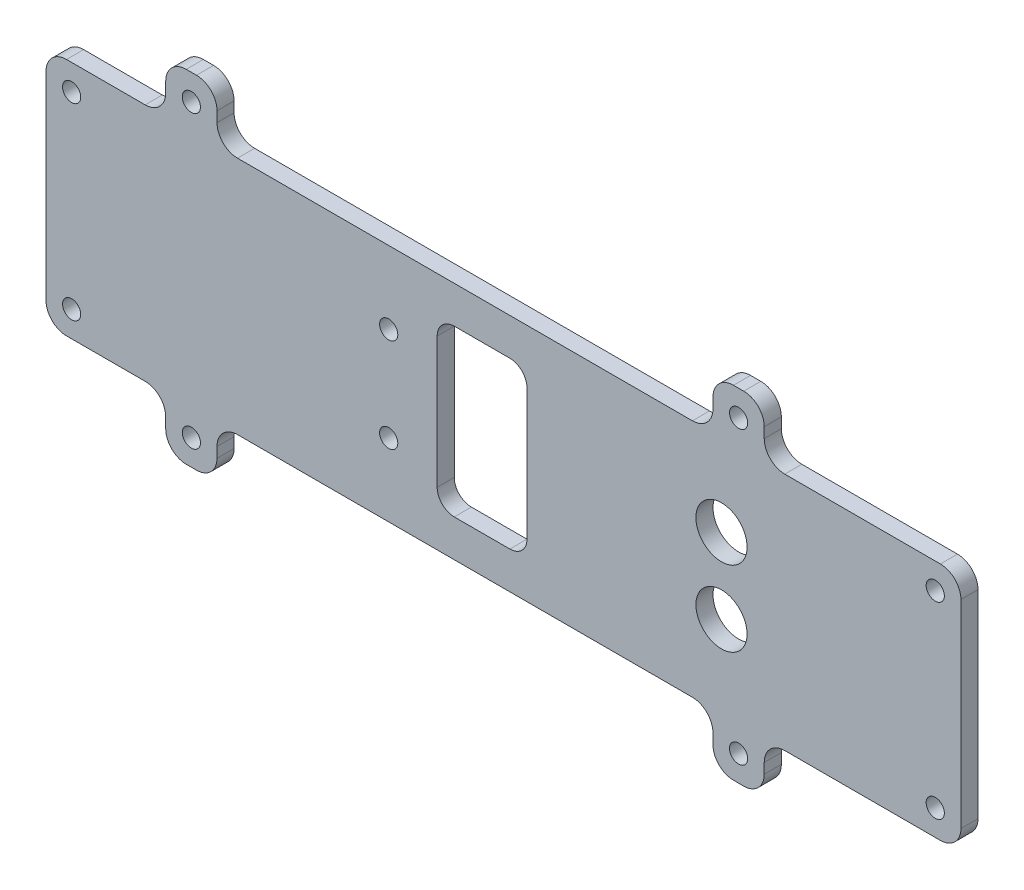
SolidWorks part; units mm, degrees
material "PC High Viscosity"
ref_plane "Front Plane" through (0, 0, 0) normal (0, 0, 1) x (1, 0, 0)
ref_plane "Top Plane" through (0, 0, 0) normal (0, 1, 0) x (1, 0, 0)
ref_plane "Right Plane" through (0, 0, 0) normal (1, 0, 0) x (0, 0, -1)
ref_plane "Plane1" through (0, 0, 0) normal (0, 0, -1) x (-1, 0, 0)
sketch "Sketch1" plane through (0, 0, 0) normal (0, 0, -1) x (-1, 0, 0)
  line L0 (-127, -44.45) -> (127, -44.45)
  line L1 (127, -44.45) -> (127, 44.45)
  line L2 (127, 44.45) -> (-127, 44.45)
  line L3 (-127, 44.45) -> (-127, -44.45)
  line L4 (13.5, 27.5) -> (13.5, -27.5)
  line L5 (13.5, -27.5) -> (-13.5, -27.5)
  line L6 (-13.5, -27.5) -> (-13.5, 27.5)
  line L7 (-13.5, 27.5) -> (13.5, 27.5)
  line L8 (0, 41.275) -> (0, -41.275) construction
  line L9 (-127, 0) -> (127, 0) construction
  line L10 (0, 27.5) -> (0, -27.5) construction
  circle A0 centre (28.58, 27.5) radius 1.85 construction
  circle A1 centre (18.58, 27.5) radius 1.85 construction
  circle A2 centre (18.58, -27.5) radius 1.85 construction
  circle A3 centre (28.58, -27.5) radius 1.85 construction
  circle A4 centre (-88.9, 14) radius 9.5
  circle A9 centre (-88.9, -14) radius 9.5
  circle A10 centre (-88.9, 14) radius 13.5 construction
  circle A11 centre (-88.9, -14) radius 13.5 construction
  point P30 (127, 0)
  point P41 (0, 0)
  dimension "D13" = 3.7
  dimension "D14" = 19
  dimension "D15" = 27
  dimension "D1" = 88.9
  dimension "D2" = 254
  dimension "D3" = 27
  dimension "D4" = 55
  dimension "D5" = 127
  dimension "D6" = 5.08
  dimension "D7" = 55
  dimension "D8" = 10
  dimension "D11" = 28
  dimension "D12" = 75.4
  dimension "D16" = 24.6
extrude "Boss-Extrude1" add sketch "Sketch1" against normal blind 6.35
sketch "Sketch4" plane through (0, 0, 6.35) normal (0, 0, 1) x (1, 0, 0)
  line L0 (127, -44.45) -> (-127, -44.45) construction
  line L1 (-117.475, 44.45) -> (-98.425, 44.45)
  line L2 (-117.475, 44.45) -> (-117.475, 63.5)
  line L3 (-117.475, 63.5) -> (-98.425, 63.5)
  line L4 (-98.425, 44.45) -> (-98.425, 63.5)
  line L5 (-127, 44.45) -> (127, 44.45) construction
  line L7 (-127, 0) -> (127, 0) construction
  line L8 (-127, -44.45) -> (-127, 44.45) construction
  line L9 (127, 44.45) -> (127, -44.45) construction
  line L10 (-117.475, -63.5) -> (-98.425, -63.5)
  line L11 (-98.425, -44.45) -> (-98.425, -63.5)
  line L12 (-117.475, -44.45) -> (-98.425, -44.45)
  line L13 (-117.475, -44.45) -> (-117.475, -63.5)
  line L14 (104.775, -44.45) -> (104.775, -63.5)
  line L15 (104.775, -44.45) -> (85.725, -44.45)
  line L16 (85.725, -44.45) -> (85.725, -63.5)
  line L17 (104.775, -63.5) -> (85.725, -63.5)
  line L18 (104.775, 63.5) -> (85.725, 63.5)
  line L19 (85.725, 44.45) -> (85.725, 63.5)
  line L20 (104.775, 44.45) -> (85.725, 44.45)
  line L21 (104.775, 44.45) -> (104.775, 63.5)
  line L27 (-107.95, 63.5) -> (95.25, 63.5) construction
  line L28 (-107.95, 63.5) -> (-107.95, -63.5) construction
  line L29 (-107.95, -63.5) -> (95.25, -63.5) construction
  line L30 (95.25, 63.5) -> (95.25, -63.5) construction
  point P29 (0, 0)
  dimension "D1" = 19.05
  dimension "D2" = 19.05
  dimension "D3" = 203.2
  dimension "D4" = 31.75
extrude "Boss-Extrude2" add sketch "Sketch4" against normal up to surface (6.35 mm away) up to face at (98.4, -14, 0)
sketch "Sketch7" plane through (0, 0, 6.35) normal (0, 0, 1) x (1, 0, 0)
  line L1 (-127, -44.45) -> (-161.925, -44.45)
  line L2 (-127, -44.45) -> (-127, 44.45)
  line L3 (-127, 44.45) -> (-161.925, 44.45)
  line L4 (-161.925, -44.45) -> (-161.925, 44.45)
  line L5 (127, -44.45) -> (177.8, -44.45)
  line L6 (127, -44.45) -> (127, 44.45)
  line L7 (127, 44.45) -> (177.8, 44.45)
  line L8 (177.8, -44.45) -> (177.8, 44.45)
  dimension "D1" = 50.8
  dimension "D6" = 34.925
extrude "Boss-Extrude3" add sketch "Sketch7" against normal up to surface (6.35 mm away) up to face at (98.4, -14, 0)
hole_wizard "1/4 Clearance Hole1" positions "Sketch2" profile "Sketch3" hole size "1/4" standard "ANSI Inch" end condition through all
sketch "Sketch2" plane through (0, 0, 6.35) normal (0, 0, 1) x (1, 0, 0)
  line L8 (-152.4, 0) -> (152.4, 0) construction
  line L9 (-98.425, 63.5) -> (-117.475, 63.5) construction
  line L12 (-107.95, 53.975) -> (95.25, 53.975) construction
  line L13 (-107.95, 53.975) -> (-107.95, -53.975) construction
  line L14 (-107.95, -53.975) -> (95.25, -53.975) construction
  line L15 (95.25, 53.975) -> (95.25, -53.975) construction
  line L16 (85.725, -63.5) -> (104.775, -63.5) construction
  line L18 (168.275, 34.925) -> (-152.4, 34.925) construction
  line L19 (168.275, 34.925) -> (168.275, -34.925) construction
  line L20 (168.275, -34.925) -> (-152.4, -34.925) construction
  line L21 (-152.4, 34.925) -> (-152.4, -34.925) construction
  line L22 (-117.475, -44.45) -> (-161.925, -44.45) construction
  line L23 (-161.925, 44.45) -> (-161.925, -44.45) construction
  line L24 (177.8, -44.45) -> (177.8, 44.45) construction
  line L25 (0, -27.5) -> (0, 27.5) construction
  line L26 (13.5, -27.5) -> (-13.5, -27.5) construction
  line L27 (-13.5, 27.5) -> (13.5, 27.5) construction
  line L29 (-12.45, 25.25) -> (12.45, 25.25) construction
  line L30 (-12.45, 25.25) -> (-12.45, -25.25) construction
  line L31 (-12.45, -25.25) -> (12.45, -25.25) construction
  line L32 (12.45, 25.25) -> (12.45, -25.25) construction
  point P65 (-107.95, 53.975)
  point P67 (95.25, 53.975)
  point P69 (95.25, -53.975)
  point P71 (-107.95, -53.975)
  point P125 (95.25, -63.5)
  point P127 (0, 0)
  point P212 (-152.4, 0)
  point P217 (168.275, -34.925)
  point P220 (168.275, 34.925)
  point P223 (-152.4, 34.925)
  point P226 (-152.4, -34.925)
  point P238 (-34.675, 17.4625)
  point P240 (-34.675, -17.4625)
  point P277 (0, 25.25)
  point P278 (-12.45, 0)
  dimension "D1" = 50.5
  dimension "D2" = 24.9
  dimension "D3" = 9.525
  dimension "D4" = 203.2
  dimension "D5" = 9.525
  dimension "D6" = 9.525
  dimension "D7" = 9.525
  dimension "D8" = 22.225
  dimension "D9" = 17.4625
sketch "Sketch3" plane through (-107.95, 53.975, 6.35) normal (1, 0, 0) x (0, -1, 0)
  line L0 (0, 0) -> (0, 6.35)
  line L1 (0, 6.35) -> (3.3782, 6.35)
  line L2 (3.3782, 6.35) -> (3.3782, 0)
  line L5 (3.3782, 0) -> (0, 0)
  line L11 (0, -6.35) -> (0, 107.95) construction
  dimension "Thru Hole Dia." = 6.7564
  dimension "Thru Hole Depth" = 6.35
fillet "Fillet1" radius 3.175 4 edges at (13.5, 27.5, 3.175) (-13.5, 27.5, 3.175) (13.5, -27.5, 3.175) (-13.5, -27.5, 3.175)
fillet "Fillet2" radius 7.62 20 edges at (85.725, -44.45, 3.175) (85.725, -63.5, 3.175) (104.775, -44.45, 3.175) (-98.425, -63.5, 3.175) (-98.425, -44.45, 3.175) (-117.475, -63.5, 3.175) (-117.475, -44.45, 3.175) (-161.925, -44.45, 3.175) (-98.425, 44.45, 3.175) (-98.425, 63.5, 3.175) (-117.475, 63.5, 3.175) (-117.475, 44.45, 3.175) (-161.925, 44.45, 3.175) (85.725, 44.45, 3.175) (85.725, 63.5, 3.175) (104.775, 63.5, 3.175) (104.775, 44.45, 3.175) (177.8, -44.45, 3.175) (104.775, -63.5, 3.175) (177.8, 44.45, 3.175)
ref_axis "Axis1" through (88.9, -14, 0) along (0, 1, 0)
ref_plane "Plane2" through (0, 0, 0) normal (0, 0, -1) x (0, 1, 0)
sketch "Sketch8" plane through (0, 0, 0) normal (0, 0, -1) x (-1, 0, 0)
  line L0 (10.325, 27.5) -> (-10.325, 27.5) construction
  line L1 (-13.5, 24.325) -> (-13.5, -24.325) construction
  line L2 (-10.325, -27.5) -> (10.325, -27.5) construction
  line L3 (13.5, -24.325) -> (13.5, 24.325) construction
  line L4 (10.325, 27.5) -> (-10.325, 27.5)
  line L5 (-13.5, 24.325) -> (-13.5, -24.325)
  line L6 (-10.325, -27.5) -> (10.325, -27.5)
  line L7 (13.5, -24.325) -> (13.5, 24.325)
  line L8 (10.325, 30.675) -> (-10.325, 30.675)
  line L9 (-16.675, 24.325) -> (-16.675, -24.325)
  line L10 (-10.325, -30.675) -> (10.325, -30.675)
  line L11 (16.675, -24.325) -> (16.675, 24.325)
  arc A0 (13.5, 24.325) -> (10.325, 27.5) centre (10.325, 24.325) ccw construction
  arc A1 (-10.325, 27.5) -> (-13.5, 24.325) centre (-10.325, 24.325) ccw construction
  arc A2 (-13.5, -24.325) -> (-10.325, -27.5) centre (-10.325, -24.325) ccw construction
  arc A3 (10.325, -27.5) -> (13.5, -24.325) centre (10.325, -24.325) ccw construction
  arc A4 (13.5, 24.325) -> (10.325, 27.5) centre (10.325, 24.325) ccw
  arc A5 (-10.325, 27.5) -> (-13.5, 24.325) centre (-10.325, 24.325) ccw
  arc A6 (-13.5, -24.325) -> (-10.325, -27.5) centre (-10.325, -24.325) ccw
  arc A7 (10.325, -27.5) -> (13.5, -24.325) centre (10.325, -24.325) ccw
  arc A8 (-10.325, 30.675) -> (-16.675, 24.325) centre (-10.325, 24.325) ccw
  arc A9 (-16.675, -24.325) -> (-10.325, -30.675) centre (-10.325, -24.325) ccw
  arc A10 (10.325, -30.675) -> (16.675, -24.325) centre (10.325, -24.325) ccw
  arc A11 (16.675, 24.325) -> (10.325, 30.675) centre (10.325, 24.325) ccw
  dimension "D1" = 3.175
extrude "Cut-Extrude1" cut sketch "Sketch8" against normal through all
